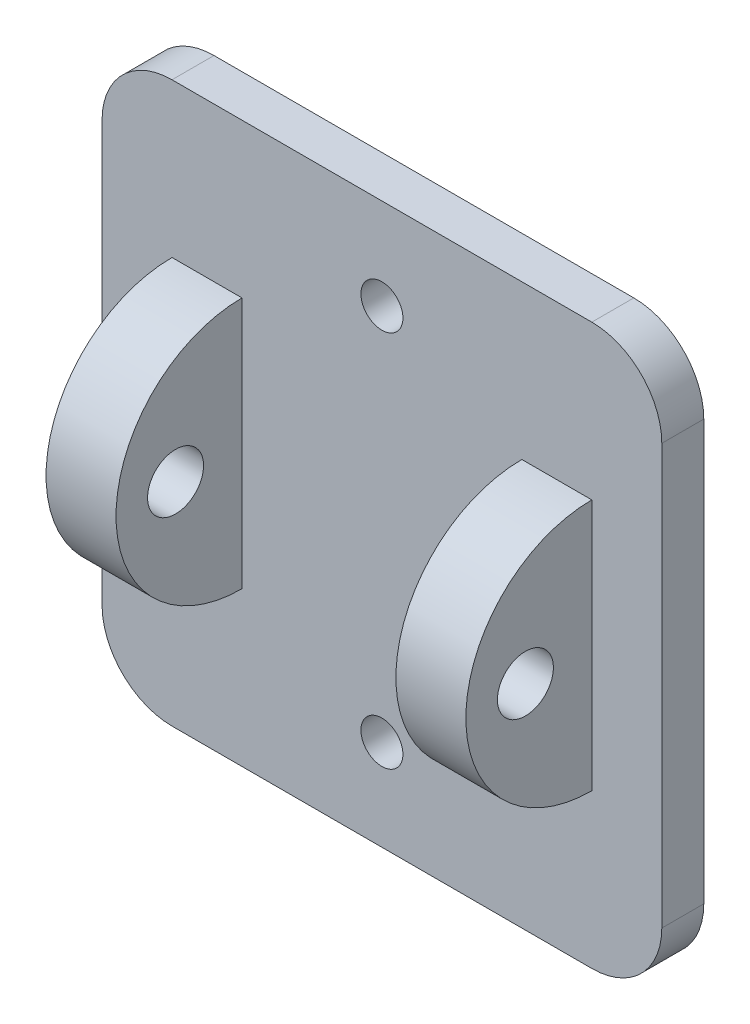
SolidWorks part; units mm, degrees
ref_plane "Alzado" through (0, 0, 0) normal (0, 0, 1) x (1, 0, 0)
ref_plane "Planta" through (0, 0, 0) normal (0, 1, 0) x (1, 0, 0)
ref_plane "Vista lateral" through (0, 0, 0) normal (1, 0, 0) x (0, 0, -1)
sketch "Croquis1" plane through (0, 0, 0) normal (0, 0, 1) x (1, 0, 0)
  line L0 (7.3124, 13.7981) -> (7.3124, -26.2019) construction
  line L1 (-7.6876, 13.7981) -> (22.3124, 13.7981)
  line L2 (-12.6876, 8.7981) -> (-12.6876, -21.2019)
  line L3 (-7.6876, -26.2019) -> (22.3124, -26.2019)
  line L4 (27.3124, 8.7981) -> (27.3124, -21.2019)
  arc A0 (-12.6876, -21.2019) -> (-7.6876, -26.2019) centre (-7.6876, -21.2019) ccw
  arc A1 (22.3124, -26.2019) -> (27.3124, -21.2019) centre (22.3124, -21.2019) ccw
  arc A2 (22.3124, 13.7981) -> (27.3124, 8.7981) centre (22.3124, 8.7981) cw
  arc A3 (-7.6876, 13.7981) -> (-12.6876, 8.7981) centre (-7.6876, 8.7981) ccw
  circle A4 centre (7.3124, 7.2981) radius 1.5
  circle A5 centre (7.3124, -19.7019) radius 1.5
  point P8 (27.3124, -26.2019)
  point P11 (27.3124, 13.7981)
  point P14 (-12.6876, 13.7981)
  dimension "D3" = 5
  dimension "D4" = 3
  dimension "D1" = 40
  dimension "D2" = 40
  dimension "D5" = 27
  dimension "D6" = 6.5
extrude "Saliente-Extruir1" add sketch "Croquis1" along normal blind 3
sketch "Croquis2" plane through (0, 0, 0) normal (0, 0, 1) x (1, 0, 0)
  line L0 (7.3124, 13.7981) -> (7.3124, -26.2019) construction
  line L1 (-7.6876, 2.7981) -> (-2.6876, 2.7981)
  line L2 (-7.6876, 2.7981) -> (-7.6876, -15.2019)
  line L3 (-7.6876, -15.2019) -> (-2.6876, -15.2019)
  line L4 (-2.6876, 2.7981) -> (-2.6876, -15.2019)
  line L5 (22.3124, 13.7981) -> (-7.6876, 13.7981) construction
  line L6 (-7.6876, -26.2019) -> (22.3124, -26.2019) construction
  line L7 (-12.6876, 8.7981) -> (-12.6876, -21.2019) construction
  line L8 (22.3124, -15.2019) -> (17.3124, -15.2019)
  line L9 (22.3124, 2.7981) -> (22.3124, -15.2019)
  line L10 (17.3124, 2.7981) -> (17.3124, -15.2019)
  line L11 (22.3124, 2.7981) -> (17.3124, 2.7981)
  dimension "D1" = 5
  dimension "D2" = 18
  dimension "D3" = 11
  dimension "D4" = 5
extrude "Saliente-Extruir2" add sketch "Croquis2" along normal blind 9 from surface starting at face at (8.8124, 7.2981, 3)
fillet "Redondeo6" 2 edges at (-5.1876, -15.2019, 12) (-5.1876, 2.7981, 12) type full round first side face at (-5.1876, -15.2019, 7.5) second side face at (-5.1876, 2.7981, 7.5) middle face at (-5.1876, -6.2019, 12)
fillet "Redondeo7" 2 edges at (19.8124, -15.2019, 12) (19.8124, 2.7981, 12) type full round first side face at (19.8124, -15.2019, 7.5) second side face at (19.8124, 2.7981, 7.5) middle face at (19.8124, -6.2019, 12)
sketch "Croquis3" plane through (-7.6876, 0, 0) normal (-1, 0, 0) x (0, 0, 1)
  line L0 (3, -6.2019) -> (7.7463, -6.2019) construction
  line L1 (3, 8.7981) -> (3, -21.2019) construction
  circle A0 centre (7.7463, -6.2019) radius 2
  dimension "D2" = 4
  dimension "D1" = 4.7463
extrude "Cortar-Extruir1" cut sketch "Croquis3" against normal up to surface (30 mm away) contours A0 up to face at (22.3124, -6.2019, 7.5)
